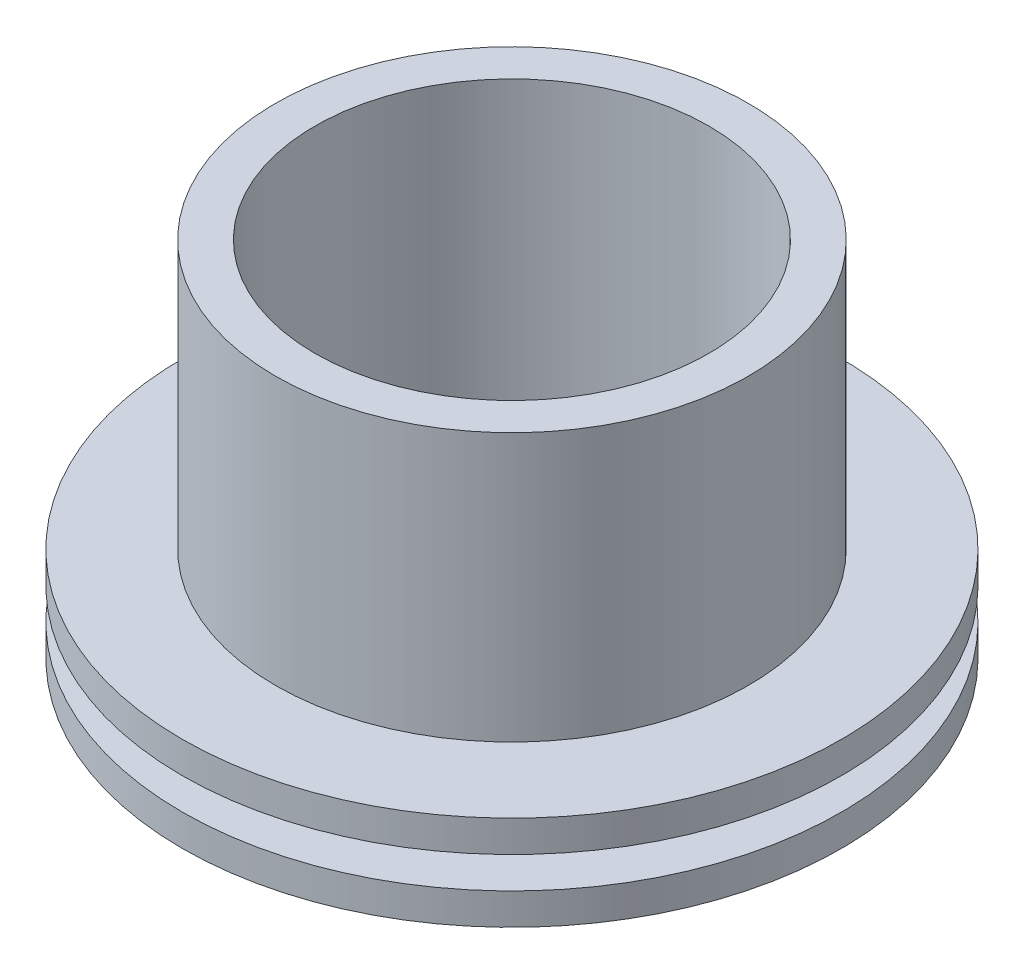
SolidWorks part; units mm, degrees
ref_plane "Front Plane" through (0, 0, 0) normal (0, 0, 1) x (1, 0, 0)
ref_plane "Top Plane" through (0, 0, 0) normal (0, 1, 0) x (1, 0, 0)
ref_plane "Right Plane" through (0, 0, 0) normal (1, 0, 0) x (0, 0, -1)
sketch "Sketch1" plane through (0, 0, 0) normal (0, 1, 0) x (1, 0, 0)
  circle A0 centre (0, 0) radius 12.5
  circle A1 centre (0, 0) radius 15.9134
  circle A2 centre (0, 0) radius 20.9134
  circle A3 centre (0, 0) radius 15
  dimension "D1" = 25
  dimension "D2" = 31.8269
  dimension "D3" = 41.8269
  dimension "D4" = 30
extrude "Boss-Extrude1" add sketch "Sketch1" along normal blind 17 contours A3 A0 region at (-14.5757, 0, 0)
extrude "Boss-Extrude2" add sketch "Sketch1<3>" against normal blind 6 contours A2 A1 | A1 A3 | A3 A0 region at (-15.4633, 0, 0) region at (-20.3219, 0, 0) region at (-14.5757, 0, 0)
sketch "Sketch1<3>" plane through (0, 0, 0) normal (0, 1, 0) x (1, 0, 0) same geometry as "Sketch1"
extrude "Cut-Extrude1" cut sketch "Sketch1<4>" against normal blind 2 from offset 2 contours A2 A1 region at (-20.3219, 0, 0)
sketch "Sketch1<4>" plane through (0, 0, 0) normal (0, 1, 0) x (1, 0, 0) same geometry as "Sketch1"
equation "\"D3@Sketch1\" = \"CableDrumDiameter\" + ( \"MaxCableWraps\" + 1 ) * \"CableDiameter\""
equation "\"CableDiameter\"= 2"
equation "\"MaxCableExtension\"= 400"
equation "\"MaxCableWraps\"= 4"
equation "\"CableDrumDiameter\"= \"MaxCableExtension\" / \"MaxCableWraps\" / 3.142"
equation "\"D2@Sketch1\"=\"CableDrumDiameter\""
equation "\"D1@Boss-Extrude2\"=\"CableDiameter\"+4"
equation "\"D1@Cut-Extrude1\"=\"CableDiameter\""
equation "\"D1@Boss-Extrude1\"= 18 - \"CableDiameter\" / 2"
